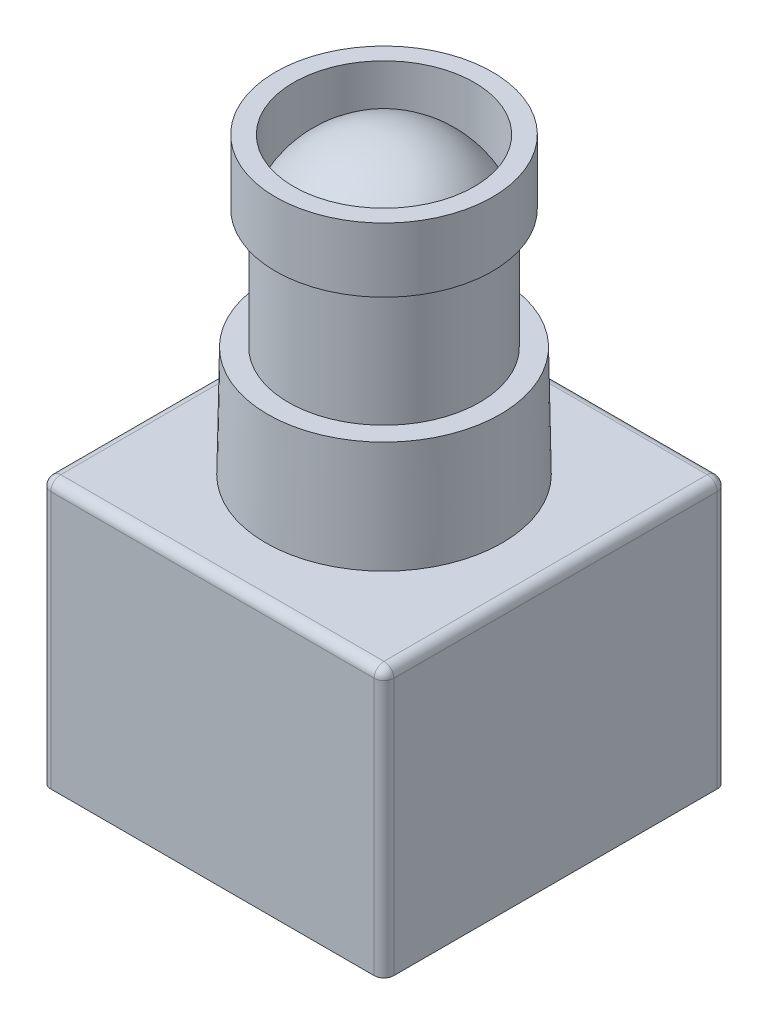
SolidWorks part; units mm, degrees
ref_plane "Front Plane" through (0, 0, 0) normal (0, 0, 1) x (1, 0, 0)
ref_plane "Top Plane" through (0, 0, 0) normal (0, 1, 0) x (1, 0, 0)
ref_plane "Right Plane" through (0, 0, 0) normal (1, 0, 0) x (0, 0, -1)
sketch "Sketch1" plane through (0, 0, 0) normal (0, 1, 0) x (1, 0, 0)
  line L1 (0, 0) -> (22.098, 0)
  line L2 (0, 0) -> (0, 22.098)
  line L3 (0, 22.098) -> (22.098, 22.098)
  line L4 (22.098, 0) -> (22.098, 22.098)
  dimension "D1" = 22.098
  dimension "D2" = 22.098
extrude "Extrude1" add sketch "Sketch1" along normal blind 17.2212
fillet "Fillet1" radius 0.635 8 edges at (11.049, 17.2212, -22.098) (22.098, 17.2212, -11.049) (11.049, 17.2212, 0) (0, 17.2212, -11.049) (0, 8.6106, -22.098) (22.098, 8.6106, -22.098) (22.098, 8.6106, 0) (0, 8.6106, 0)
sketch "Sketch2" plane through (0, 17.2212, 0) normal (0, 1, 0) x (1, 0, 0)
  line L0 (11.049, 0.635) -> (11.049, 21.463) construction
  line L1 (0.635, 0.635) -> (21.463, 0.635) construction
  line L2 (21.463, 21.463) -> (0.635, 21.463) construction
  circle A0 centre (11.049, 11.049) radius 7.62
  dimension "D1" = 15.24
extrude "Extrude2" add sketch "Sketch2" along normal blind 7.112 draft 1
sketch "Sketch3" plane through (0, 24.3332, 0) normal (0, 1, 0) x (1, 0, 0)
  circle A0 centre (11.049, 11.049) radius 6.1651
extrude "Extrude3" add sketch "Sketch3" along normal blind 7.7216
sketch "Sketch4" plane through (0, 32.0548, 0) normal (0, 1, 0) x (1, 0, 0)
  circle A0 centre (11.049, 11.049) radius 6.985
  dimension "D1" = 13.97
extrude "Extrude4" add sketch "Sketch4" along normal blind 4.1402
sketch "Sketch5" plane through (0, 36.195, 0) normal (0, 1, 0) x (1, 0, 0)
  circle A0 centre (11.049, 11.049) radius 5.8172
extrude "Extrude5" cut sketch "Sketch5" against normal blind 3.683
dome "Dome1" faces to dome 1 distance 3.683 reverse direction no elliptical dome no face at (11.049, 32.512, -5.2318) parameters "D1"=3.683
ref_plane "mid_1" through (11.049, 0, 0) normal (-1, 0, 0) x (0, 0, 1)
ref_plane "mid_2" through (0, 0, -11.049) normal (0, 0, -1) x (-1, 0, 0)
